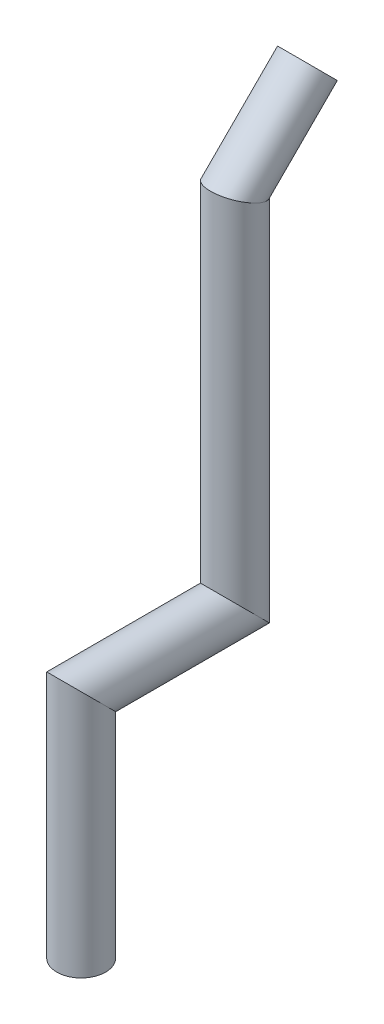
SolidWorks part; units mm, degrees
material "Silicon Rubber"
ref_plane "Front Plane" through (0, 0, 0) normal (0, 0, 1) x (1, 0, 0)
ref_plane "Top Plane" through (0, 0, 0) normal (0, 1, 0) x (1, 0, 0)
ref_plane "Right Plane" through (0, 0, 0) normal (1, 0, 0) x (0, 0, -1)
sketch "Sketch2" plane through (0, 0, 0) normal (0, 1, 0) x (1, 0, 0)
  line L0 (0, 2.5) -> (0, 8) construction
  line L1 (-17.5, 0) -> (17.5, 0) construction
  circle A0 centre (0, 0) radius 17.5 construction
  circle A1 centre (0, 0) radius 2.5 construction
  circle A2 centre (0, 8) radius 3.175
  circle A3 centre (0, 8) radius 4.7625
  circle A4 centre (0, -8) radius 3.175 construction
  circle A5 centre (0, -8) radius 4.7625 construction
  dimension "D1" = 35
  dimension "D2" = 5
  dimension "D4" = 6.35
  dimension "D5" = 9.525
  dimension "D3" = 5.5
sketch "Sketch4" plane through (0, 0, 0) normal (1, 0, 0) x (0, 0, -1)
  line L0 (8, 0) -> (8, 45)
  line L1 (8, 45) -> (38, 45)
  line L2 (38, 45) -> (38, 115)
  line L4 (38, 115) -> (52.1421, 129.1421)
  line L5 (38, 115) -> (63.0677, 115) construction
  dimension "D1" = 45
  dimension "D2" = 30
  dimension "D3" = 70
  dimension "D4" = 20
  dimension "D5" = 45
sweep "Sweep2" add profiles "Sketch2" path "Sketch4"
ref_plane "Plane2" through (0, 87.1066, -87.1066) normal (0, 0.7071, -0.7071) x (1, 0, 0)
sketch "Sketch11" plane through (0, 87.1066, -87.1066) normal (0, 0.7071, -0.7071) x (1, 0, 0)
  line L0 (0, -49.6847) -> (0, -59.2097) construction
  line L1 (-4.7625, -54.4472) -> (4.7625, -54.4472) construction
  line L2 (0, -49.6847) -> (2, -49.6847) construction
  line L3 (0, -49.6847) -> (-2, -49.6847) construction
  line L4 (-2, -49.6847) -> (-2, -54.4472)
  line L5 (-2, -54.4472) -> (2, -54.4472)
  line L6 (2, -54.4472) -> (2, -49.6847)
  line L7 (2, -49.6847) -> (-2, -49.6847)
  circle A0 centre (0, -54.4472) radius 4.7625 construction
  dimension "D1" = 2
extrude "Cut-Extrude2" cut sketch "Sketch11" against normal blind 8
